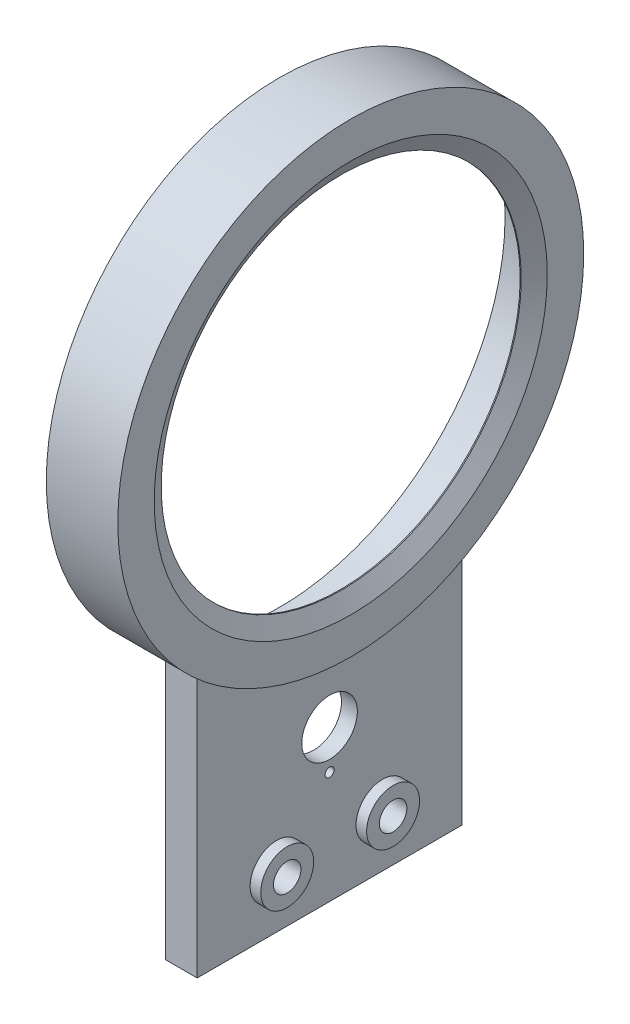
SolidWorks part; units mm, degrees
ref_plane "Front Plane" through (0, 0, 0) normal (0, 0, 1) x (1, 0, 0)
ref_plane "Top Plane" through (0, 0, 0) normal (0, 1, 0) x (1, 0, 0)
ref_plane "Right Plane" through (0, 0, 0) normal (1, 0, 0) x (0, 0, -1)
sketch "Sketch1" plane through (0, 0, 0) normal (1, 0, 0) x (0, 0, -1)
  line L0 (0, -6) -> (0, 6) construction
  line L1 (-7.5, 0) -> (7.5, 0) construction
  circle A0 centre (0, 0) radius 42.65
  circle A1 centre (0, 0) radius 44
  circle A2 centre (0, 0) radius 2.1 construction
  circle A3 centre (0, 6) radius 1.5 construction
  circle A4 centre (7.5, 0) radius 1.5 construction
  circle A5 centre (0, -6) radius 1.5 construction
  circle A6 centre (-7.5, 0) radius 1.5 construction
  circle A7 centre (0, 0) radius 34
  point P7 (0, 0)
  point P11 (0, 0)
  dimension "D1" = 88
  dimension "D2" = 85.3
  dimension "D3" = 4.2
  dimension "D6" = 3
  dimension "D7" = 3
  dimension "D8" = 3
  dimension "D9" = 3
  dimension "D10" = 68
  dimension "D4" = 15
  dimension "D5" = 12
extrude "Boss-Extrude1" add sketch "Sketch1" against normal blind 11.5 contours A1 A0 region at (0, 0, 42.7555)
extrude "Boss-Extrude2" add sketch "Sketch1<2>" along normal blind 2 contours A0 | A1 A0 region at (0, 0, 41.4437) region at (0, 0, 42.7555)
sketch "Sketch1<2>" plane through (0, 0, 0) normal (1, 0, 0) x (0, 0, -1) same geometry as "Sketch1"
ref_plane "Plane1" through (-2, 0, 0) normal (1, 0, 0) x (0, 0, -1)
sketch "Sketch5" plane through (-2, 0, 0) normal (1, 0, 0) x (0, 0, -1)
  line L0 (0, 0) -> (0, -78.2719) construction
  line L1 (-25, -44) -> (25, -44) construction
  line L2 (-25, -86) -> (25, -86)
  line L3 (-25, -86) -> (-25, -36.2077)
  line L5 (25, -86) -> (25, -36.2077)
  circle A0 centre (0, 0) radius 44 construction
  circle A2 centre (0, 0) radius 44
  circle A5 centre (0, 0) radius 44
  point P12 (0, -44)
  dimension "D1" = 50
  dimension "D2" = 25
  dimension "D3" = 42
  dimension "D4" = 0
extrude "Boss-Extrude3" add sketch "Sketch5" against normal blind 6 contours L2 L5 L3 | L5 L2 L3 region at (-2, -63.6922, 0)
sketch "Sketch7" plane through (0, 0, 0) normal (-1, 0, 0) x (0, 0, 1)
  circle A0 centre (0, 0) radius 42.65
  circle A1 centre (0, 0) radius 39.5
  dimension "D1" = 85.3
  dimension "D2" = 79
extrude "Boss-Extrude4" add sketch "Sketch7" along normal blind 1
sketch "Sketch8" plane through (-2, 0, 0) normal (1, 0, 0) x (0, 0, -1)
  line L0 (0, 0) -> (0, -57.5) construction
  line L1 (0, -57.5) -> (0, -64.86) construction
  line L2 (-25, -86) -> (25, -86) construction
  line L3 (-25, -86) -> (-25, -36.2077) construction
  line L4 (25, -86) -> (25, -36.2077) construction
  circle A0 centre (0, -57.5) radius 5.25
  circle A1 centre (0, -64.86) radius 0.85
  circle A2 centre (-10, -76) radius 2.6
  circle A3 centre (10, -76) radius 2.6
  dimension "D2" = 10.5
  dimension "D4" = 1.7
  dimension "D7" = 5.2
  dimension "D10" = 5.2
  dimension "D1" = 57.5
  dimension "D3" = 7.36
  dimension "D5" = 10
  dimension "D6" = 15
  dimension "D8" = 15
  dimension "D9" = 10
extrude "Cut-Extrude3" cut sketch "Sketch8" against normal blind 10
sketch "Sketch9" plane through (-8, 0, 0) normal (-1, 0, 0) x (0, 0, 1)
  circle A0 centre (0, -57.5) radius 12.5
  dimension "D1" = 25
extrude "Cut-Extrude4" cut sketch "Sketch9" against normal blind 3
chamfer "Chamfer1" distance 1.8 angle 60 1 edges at (2, 0, -34) first distance on face at (2, 0, -34)
sketch "Sketch11" plane through (-2, 0, 0) normal (-1, 0, 0) x (0, 0, 1)
  circle A0 centre (-10, -76) radius 5
  circle A1 centre (10, -76) radius 5
  circle A2 centre (-10, -76) radius 2.6
  circle A3 centre (10, -76) radius 2.6
  dimension "D1" = 5.2
  dimension "D2" = 5.2
  dimension "D3" = 10
  dimension "D4" = 10
extrude "Boss-Extrude5" add sketch "Sketch11" against normal blind 2
sketch "Sketch10" plane through (-2, 0, 0) normal (1, 0, 0) x (0, 0, -1)
  line L0 (-25, -86) -> (25, -86) construction
  line L1 (-28, -87.9871) -> (28, -87.9871)
  line L2 (-28, -87.9871) -> (-28, -44)
  line L3 (-28, -44) -> (28, -44)
  line L4 (28, -87.9871) -> (28, -44)
  line L6 (-54.3493, 51.4543) -> (51.6324, 51.4543)
  line L7 (-54.3493, 51.4543) -> (-54.3493, -95.2896)
  line L8 (-54.3493, -95.2896) -> (51.6324, -95.2896)
  line L9 (51.6324, 51.4543) -> (51.6324, -95.2896)
  circle A0 centre (0, 0) radius 44 construction
  point P6 (0, -86)
  point P7 (0, -87.9871)
  dimension "D1" = 56
extrude "Cut-Extrude5" [suppressed] cut sketch "Sketch10" against normal through all both and the other way through all
equation "\"D2@Sketch5\"=\"D1@Sketch5\"/2"
